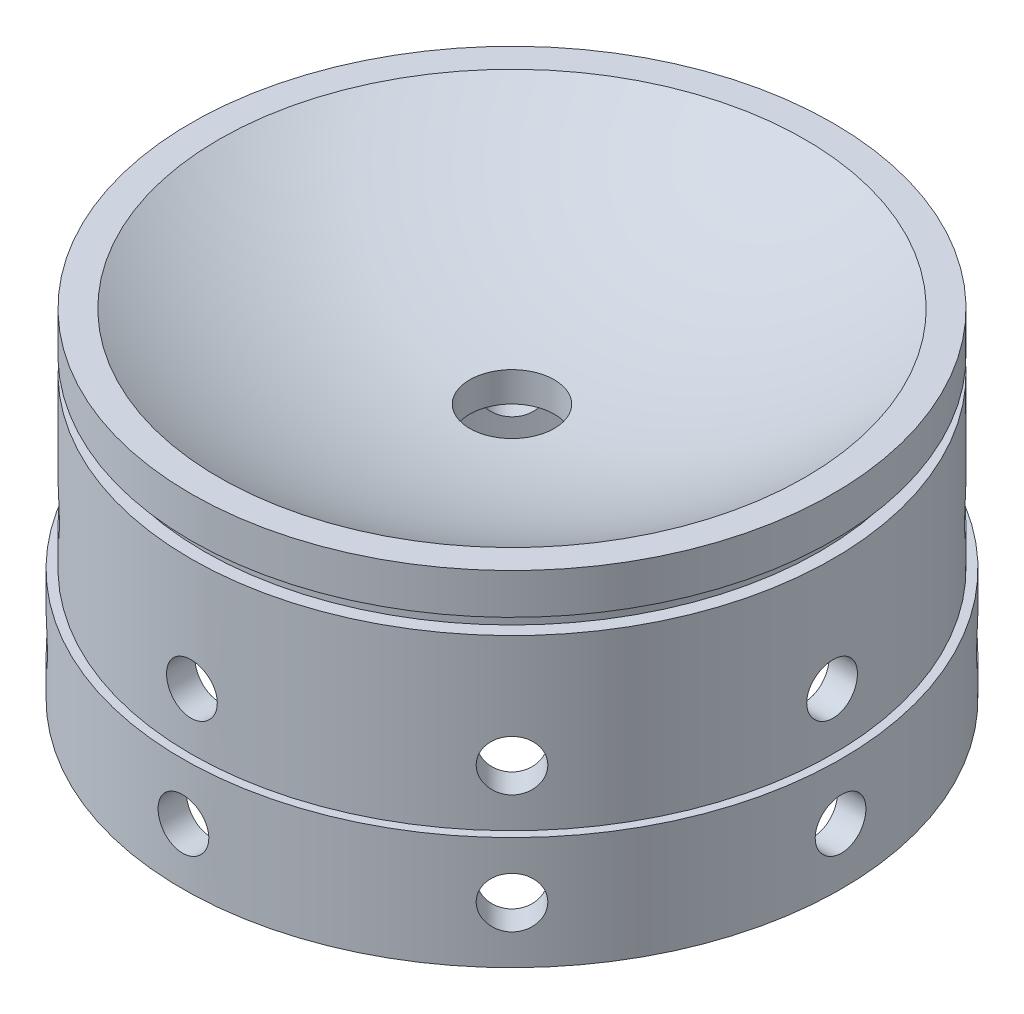
SolidWorks part; units mm, degrees
ref_plane "Front Plane" through (0, 0, 0) normal (0, 0, 1) x (1, 0, 0)
ref_plane "Top Plane" through (0, 0, 0) normal (0, 1, 0) x (1, 0, 0)
ref_plane "Right Plane" through (0, 0, 0) normal (1, 0, 0) x (0, 0, -1)
sketch "Sketch1" plane through (0, 0, 0) normal (0, 0, 1) x (1, 0, 0)
  line L0 (0, 0) -> (0, 6.35)
  line L1 (0, 0) -> (72.39, 0)
  line L2 (72.39, 0) -> (72.39, 12.7)
  line L3 (72.39, 12.7) -> (69.469, 12.7)
  line L4 (69.469, 12.7) -> (69.469, 16.256)
  line L5 (69.469, 16.256) -> (72.39, 16.256)
  line L6 (72.39, 16.256) -> (72.39, 25.4)
  line L9 (72.39, 6.35) -> (0, 6.35) construction
  line L10 (72.39, 0) -> (72.39, -25.4)
  line L11 (72.39, -25.4) -> (66.04, -25.4)
  line L12 (66.04, -25.4) -> (66.04, 0)
  line L13 (74.93, 68.1653) -> (74.93, 53.6699) construction
  line L14 (67.945, -50.8) -> (67.945, -25.4)
  line L15 (67.945, -50.8) -> (74.295, -50.8)
  line L16 (9.525, 6.7164) -> (9.525, 0)
  line L17 (73.025, 45.3691) -> (73.025, 21.7883) construction
  line L18 (74.295, -50.8) -> (74.295, -25.4)
  line L19 (74.295, -25.4) -> (72.39, -25.4)
  line L20 (72.39, 25.4) -> (66.04, 25.4)
  arc A1 (0, 6.35) -> (66.04, 25.4) centre (0, 130.3443) ccw
  dimension "D1" = 72.39
  dimension "D9" = 6.35
  dimension "D12" = 9.525
  dimension "D3" = 12.7
  dimension "D4" = 3.556
  dimension "D2" = 73.025
  dimension "D13" = 3.556
  dimension "D6" = 6.35
  dimension "D7" = 25.4
  dimension "D8" = 74.93
  dimension "D10" = 25.4
  dimension "D11" = 74.295
  dimension "D5" = 25.4
  dimension "D14" = 6.35
revolve "Revolve1" add sketch "Sketch1" angle 360 about L0 region at (48.3195, 8.6296, 0) region at (69.215, -12.7, 0) region at (71.12, -38.1, 0)
hole_wizard "1/2 (0.45) Diameter Hole3" positions "3DSketch5" profile "Sketch8" hole size "1/2" standard "ANSI Inch"
sketch3d "3DSketch5"
  line L0 (0, -25.4, 0) -> (0, 0, 0) construction
  line L2 (0, -12.7, 0) -> (72.39, -12.7, 0)
  circle A8 centre (0, -25.4, 0) radius 72.39 construction
  circle A9 centre (0, -25.4, 0) radius 72.39
  point P0 (72.39, -12.7, 0)
  point P41 (0, -97.79, 0)
  point P43 (0, -97.79, 0)
  point P53 (72.39, -12.7, 0)
sketch "Sketch8" plane through (72.39, -12.7, 0) normal (0, 1, 0) x (0, 0, -1)
  line L0 (0, 0) -> (0, 75.8229)
  line L1 (0, 75.8229) -> (5.715, 72.389)
  line L2 (5.715, 72.389) -> (5.715, 0)
  line L5 (5.715, 0) -> (0, 0)
  line L10 (0, 75.8229) -> (-5.715, 72.389) construction
  line L11 (0, -6.35) -> (0, 107.95) construction
  dimension "Hole Dia." = 11.43
  dimension "Hole Depth" = 72.389
  dimension "Drill Angle" = 118
hole_wizard "1/2 (0.45) Diameter Hole2" positions "3DSketch6" profile "Sketch9" hole size "1/2" standard "ANSI Inch"
sketch3d "3DSketch6"
  line L0 (0, -25.4, 0) -> (0, -50.8, 0)
  line L2 (0, -38.1, 0) -> (74.295, -38.1, 0)
  circle A0 centre (0, -50.8, 0) radius 74.295 construction
  circle A1 centre (0, -25.4, 0) radius 74.295 construction
  circle A2 centre (0, -50.8, 0) radius 74.295
  circle A3 centre (0, -25.4, 0) radius 74.295
  point P0 (74.295, -38.1, 0)
  point P5 (0, -125.095, 0)
  point P8 (0, -99.695, 0)
  point P10 (0, -125.095, 0)
  point P12 (0, -99.695, 0)
sketch "Sketch9" plane through (74.295, -38.1, 0) normal (0, 1, 0) x (0, 0, -1)
  line L0 (0, 0) -> (0, 77.7279)
  line L1 (0, 77.7279) -> (5.715, 74.294)
  line L2 (5.715, 74.294) -> (5.715, 0)
  line L5 (5.715, 0) -> (0, 0)
  line L10 (0, 77.7279) -> (-5.715, 74.294) construction
  line L11 (0, -6.35) -> (0, 107.95) construction
  dimension "Hole Dia." = 11.43
  dimension "Hole Depth" = 74.294
  dimension "Drill Angle" = 118
ref_axis "CenterAxis" through (0, 6.7164, 0) along (0, -1, 0)
chamfer "Chamfer1" distance 2.54 angle 45 1 edges at (0, -25.4, -67.945)
pattern_circular "CirPattern1" count 8 over 360 about axis through (0, -25.4, 0) along (0, -1, 0) of "1/2 (0.45) Diameter Hole3", "1/2 (0.45) Diameter Hole2"
equation "\"D1@Sketch1\"=(5.75/2)-(0.025in)"
equation "\"D12@Sketch1\"=0.75/2"
equation "\"D2@Sketch1\"=5.75/2"
equation "\"D8@Sketch1\"=5.9/2"
equation "\"D11@Sketch1\"=5.9/2 - (0.025in)"
